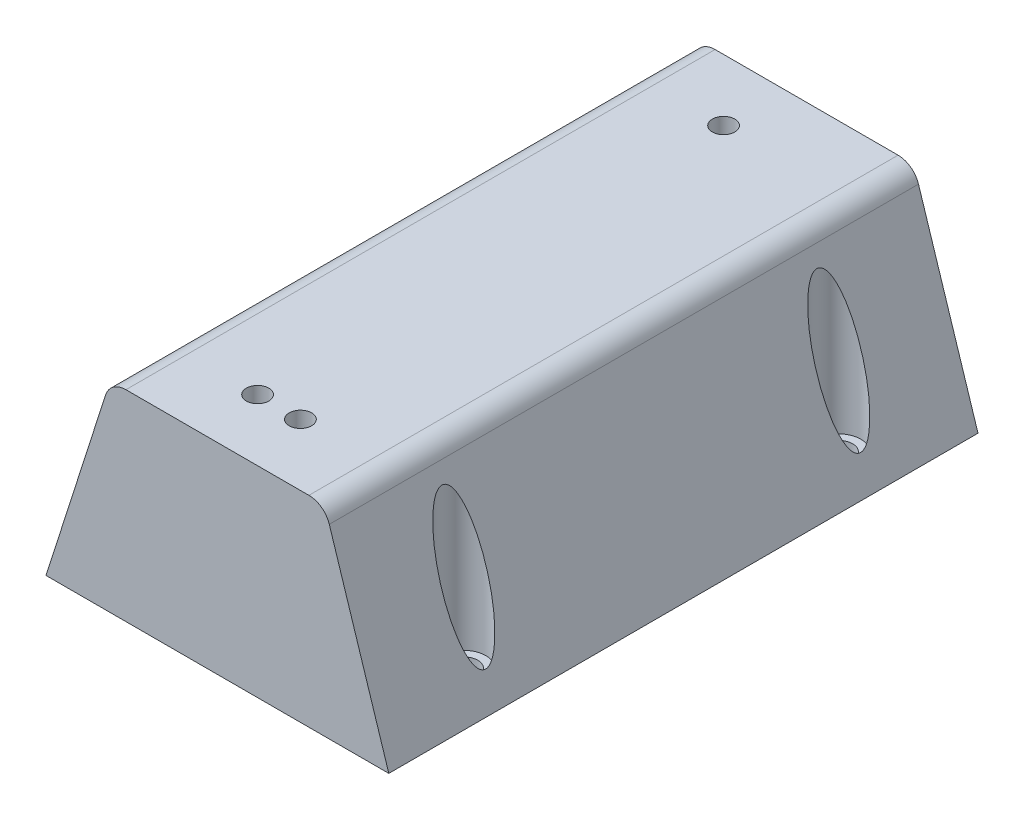
SolidWorks part; units mm, degrees
ref_plane "Front Plane" through (0, 0, 0) normal (0, 0, 1) x (1, 0, 0)
ref_plane "Top Plane" through (0, 0, 0) normal (0, 1, 0) x (1, 0, 0)
ref_plane "Right Plane" through (0, 0, 0) normal (1, 0, 0) x (0, 0, -1)
sketch "Sketch2" plane through (0, 0, 0) normal (0, 0, 1) x (1, 0, 0)
  line L0 (10, -1.25) -> (10, -17.5)
  line L1 (-10, -1.25) -> (10, -1.25)
  line L2 (-10, -1.25) -> (-10, 1.25) construction
  line L3 (-10, 1.25) -> (10, 1.25)
  line L4 (10, -1.25) -> (10, 1.25) construction
  line L5 (-10, -1.25) -> (10, 1.25) construction
  line L6 (-10, 1.25) -> (10, -1.25) construction
  line L7 (10, -17.5) -> (16, -17.5)
  line L8 (16, -17.5) -> (10, 1.25)
  line L9 (0, 0) -> (0, -7.3093) construction
  line L10 (-10, -17.5) -> (-16, -17.5)
  line L11 (-16, -17.5) -> (-10, 1.25)
  line L12 (-10, -1.25) -> (-10, -17.5)
  point P0 (0, 0)
  dimension "D1" = 2.5
  dimension "D2" = 20
  dimension "D3" = 6
  dimension "D4" = 16.25
extrude "Boss-Extrude1" add sketch "Sketch2" along normal mid plane 50
sketch "Sketch3" plane through (0, 0, 25) normal (0, 0, 1) x (1, 0, 0)
  line L0 (-10, -17.5) -> (10, -17.5)
  line L8 (16, -17.5) -> (10, 1.25)
  line L9 (10, 1.25) -> (-10, 1.25)
  line L10 (-10, 1.25) -> (-16, -17.5)
  line L11 (-16, -17.5) -> (-10, -17.5)
  line L12 (-10, -17.5) -> (-10, -1.25)
  line L13 (-10, -1.25) -> (10, -1.25)
  line L14 (10, -1.25) -> (10, -17.5)
  line L15 (10, -17.5) -> (16, -17.5)
  line L16 (16, -17.5) -> (10, 1.25)
  line L17 (10, 1.25) -> (-10, 1.25)
  line L18 (-10, 1.25) -> (-16, -17.5)
  line L19 (-16, -17.5) -> (-10, -17.5)
  line L23 (10, -17.5) -> (16, -17.5)
  dimension "D1" = 0
extrude "Boss-Extrude2" add sketch "Sketch3" along normal blind 2.5
mirror "Mirror1" about plane through (0, 0, 0) normal (0, 0, 1) of "Boss-Extrude2"
sketch "Sketch4" plane through (0, -1.25, 0) normal (0, -1, 0) x (1, 0, 0)
  line L0 (-3.27, -23.02) -> (-3.27, -20.48) construction
  line L1 (-3.27, -20.48) -> (-0.73, -20.48) construction
  line L2 (-0.73, -20.48) -> (-0.73, -23.02) construction
  line L3 (-0.73, -23.02) -> (-3.27, -23.02) construction
  line L4 (0.73, 23.02) -> (3.27, 23.02) construction
  line L5 (3.27, 23.02) -> (3.27, 20.48) construction
  line L6 (3.27, 20.48) -> (0.73, 20.48) construction
  line L7 (0.73, 20.48) -> (0.73, 23.02) construction
  line L8 (-3.27, 20.48) -> (-3.27, 23.02) construction
  line L9 (-3.27, 23.02) -> (-0.73, 23.02) construction
  line L10 (-0.73, 23.02) -> (-0.73, 20.48) construction
  line L11 (-0.73, 20.48) -> (-3.27, 20.48) construction
  line L12 (-3.27, -23.02) -> (-3.27, -20.48)
  line L13 (-3.27, -20.48) -> (-0.73, -20.48)
  line L14 (-0.73, -20.48) -> (-0.73, -23.02)
  line L15 (-0.73, -23.02) -> (-3.27, -23.02)
  line L16 (0.73, 23.02) -> (3.27, 23.02)
  line L17 (3.27, 23.02) -> (3.27, 20.48)
  line L18 (3.27, 20.48) -> (0.73, 20.48)
  line L19 (0.73, 20.48) -> (0.73, 23.02)
  line L20 (-3.27, 20.48) -> (-3.27, 23.02)
  line L21 (-3.27, 23.02) -> (-0.73, 23.02)
  line L22 (-0.73, 23.02) -> (-0.73, 20.48)
  line L23 (-0.73, 20.48) -> (-3.27, 20.48)
  circle A0 centre (-2, -21.75) radius 0.6985 construction
  circle A1 centre (2, 21.75) radius 0.6985 construction
  circle A2 centre (-2, 21.75) radius 0.6985 construction
  circle A3 centre (-2, -21.75) radius 0.6985
  circle A4 centre (2, 21.75) radius 0.6985
  circle A5 centre (-2, 21.75) radius 0.6985
sketch "Sketch5" plane through (0, -1.25, 0) normal (0, -1, 0) x (1, 0, 0)
  line L84 (-0.23, 23.52) -> (-3.77, 23.52)
  line L85 (-3.77, 23.52) -> (-3.77, 19.98)
  line L86 (-3.77, 19.98) -> (-0.23, 19.98)
  line L87 (-0.23, 19.98) -> (-0.23, 23.52)
  line L88 (-3.27, 23.02) -> (-3.27, 20.48)
  line L89 (-0.73, 23.02) -> (-3.27, 23.02)
  line L90 (-0.73, 20.48) -> (-0.73, 23.02)
  line L91 (-3.27, 20.48) -> (-0.73, 20.48)
  line L92 (-3.27, 23.02) -> (-3.27, 20.48)
  line L93 (-0.73, 23.02) -> (-3.27, 23.02)
  line L94 (-0.73, 20.48) -> (-0.73, 23.02)
  line L95 (-3.27, 20.48) -> (-0.73, 20.48)
  line L96 (3.27, 23.02) -> (0.73, 23.02)
  line L97 (3.27, 20.48) -> (3.27, 23.02)
  line L98 (0.73, 20.48) -> (3.27, 20.48)
  line L99 (0.73, 23.02) -> (0.73, 20.48)
  line L100 (3.27, 23.02) -> (0.73, 23.02)
  line L101 (3.27, 20.48) -> (3.27, 23.02)
  line L102 (0.73, 20.48) -> (3.27, 20.48)
  line L103 (0.73, 23.02) -> (0.73, 20.48)
  line L104 (-3.27, -20.48) -> (-3.27, -23.02)
  line L105 (-0.73, -20.48) -> (-3.27, -20.48)
  line L106 (-0.73, -23.02) -> (-0.73, -20.48)
  line L107 (-3.27, -23.02) -> (-0.73, -23.02)
  line L108 (-3.27, -20.48) -> (-3.27, -23.02)
  line L109 (-0.73, -20.48) -> (-3.27, -20.48)
  line L110 (-0.73, -23.02) -> (-0.73, -20.48)
  line L111 (-3.27, -23.02) -> (-0.73, -23.02)
  line L112 (3.77, 23.52) -> (0.23, 23.52)
  line L113 (0.23, 23.52) -> (0.23, 19.98)
  line L114 (0.23, 19.98) -> (3.77, 19.98)
  line L115 (3.77, 19.98) -> (3.77, 23.52)
  line L116 (-0.23, -19.98) -> (-3.77, -19.98)
  line L117 (-3.77, -19.98) -> (-3.77, -23.52)
  line L118 (-3.77, -23.52) -> (-0.23, -23.52)
  line L119 (-0.23, -23.52) -> (-0.23, -19.98)
  line L120 (10, 25) -> (10, -25) construction
  line L121 (-10, 25) -> (10, 25)
  line L122 (-10, 25) -> (-10, 17.5)
  line L123 (-10, 17.5) -> (10, 17.5)
  line L124 (10, 25) -> (10, 17.5)
  line L125 (10, 25) -> (10, -25) construction
  line L126 (-10, -25) -> (10, -25)
  line L127 (-10, -25) -> (-10, -17.5)
  line L128 (-10, -17.5) -> (10, -17.5)
  line L129 (10, -25) -> (10, -17.5)
  line L130 (-0.23, 19.98) -> (0.23, 19.98)
  line L131 (-0.23, 23.52) -> (0.23, 23.52)
  circle A1 centre (-2, 21.75) radius 0.6985
  circle A2 centre (-2, 21.75) radius 0.6985
  circle A3 centre (2, 21.75) radius 0.6985
  circle A4 centre (2, 21.75) radius 0.6985
  circle A5 centre (-2, -21.75) radius 0.6985
  circle A6 centre (-2, -21.75) radius 0.6985
  line M17 (-10, -25) -> (10, -25)
  line M18 (10, -25) -> (10, 25)
  line M19 (10, 25) -> (-10, 25)
  line M20 (-10, 25) -> (-10, -25)
  dimension "D8" = 7.5
  dimension "D9" = 7.5
  dimension "D1" = 0
  dimension "D2" = 0
  dimension "D3" = 0
  dimension "D4" = 0
  dimension "D5" = 0
  dimension "D6" = 0
  dimension "D7" = 0.5
extrude "Boss-Extrude3" add sketch "Sketch5" along normal blind 10 contours L123 L87 L86 L85 L84 L115 L114 L113 L112 M20 M18 M19 | L128 L119 L118 L117 L116 M20 M17 M18 region at (0, -1.25, 24.7864) region at (0.1823, -1.25, -21.2044)
sketch "Sketch6" plane through (0, 1.25, 0) normal (0, 1, 0) x (1, 0, 0)
  circle A0 centre (2, -21.75) radius 0.6985 construction
  circle A1 centre (-2, -21.75) radius 0.6985 construction
  circle A2 centre (-2, 21.75) radius 0.6985 construction
  circle A3 centre (2, -21.75) radius 0.6985 construction
  circle A4 centre (-2, -21.75) radius 0.6985 construction
  circle A5 centre (-2, 21.75) radius 0.6985 construction
  circle A6 centre (-2, 21.75) radius 1.0485
  circle A7 centre (-2, -21.75) radius 1.0485
  circle A8 centre (2, -21.75) radius 1.0485
  dimension "D1" = 0.35
extrude "Cut-Extrude1" cut sketch "Sketch6" against normal through all
fillet "Fillet1" radius 2 6 edges at (10, 1.25, 0) (-10, 1.25, 0) (0, -11.25, 17.5) (0, -11.25, -17.5) (-10, -1.25, 0) (10, -1.25, 0)
sketch "Sketch7" plane through (0, -17.5, 0) normal (0, -1, 0) x (1, 0, 0)
  line L0 (-16, 27.5) -> (-16, -27.5) construction
  line L1 (-16, 27.5) -> (16, 27.5) construction
  line L2 (0, -10.3125) -> (0, 10.3125) construction
  line L3 (10.3125, 0) -> (-10.3125, 0) construction
  circle A0 centre (-13, 17.5) radius 1.25
  circle A1 centre (13, 17.5) radius 1.25
  circle A2 centre (13, -17.5) radius 1.25
  circle A3 centre (-13, -17.5) radius 1.25
  point P0 (-13, 17.5)
  point P8 (13, 17.5)
  point P12 (13, -17.5)
  point P14 (-13, -17.5)
  dimension "D3" = 2.5
  dimension "D1" = 3
  dimension "D2" = 10
hole_wizard "M2 Clearance Hole1" positions "Sketch7" profile "Sketch8" hole size "M2" standard "ANSI Metric" end condition through all
sketch "Sketch8" plane through (-13, -17.5, 17.5) normal (1, 0, 0) x (0, 0, -1)
  line L0 (0, 0) -> (0, 18.75)
  line L1 (0, 18.75) -> (1.3, 18.75)
  line L2 (1.3, 18.75) -> (1.3, 0)
  line L5 (1.3, 0) -> (0, 0)
  line L11 (0, -6.35) -> (0, 107.95) construction
  dimension "Thru Hole Dia." = 2.6
  dimension "Thru Hole Depth" = 18.75
ref_plane "Plane1" through (0, -15.5, 0) normal (0, -1, 0) x (-1, 0, 0)
sketch "Sketch9" plane through (0, -15.5, 0) normal (0, -1, 0) x (1, 0, 0)
  circle A0 centre (-13, -17.5) radius 1.3 construction
  circle A1 centre (13, -17.5) radius 1.3 construction
  circle A2 centre (13, 17.5) radius 1.3 construction
  circle A3 centre (-13, 17.5) radius 1.3 construction
  circle A4 centre (-13, -17.5) radius 1.3 construction
  circle A5 centre (13, -17.5) radius 1.3 construction
  circle A6 centre (13, 17.5) radius 1.3 construction
  circle A7 centre (-13, 17.5) radius 1.3 construction
  circle A8 centre (-13, -17.5) radius 2.05
  circle A9 centre (13, -17.5) radius 2.05
  circle A10 centre (13, 17.5) radius 2.05
  circle A11 centre (-13, 17.5) radius 2.05
  dimension "D1" = 0.75
extrude "Cut-Extrude4" cut sketch "Sketch9" against normal through all
